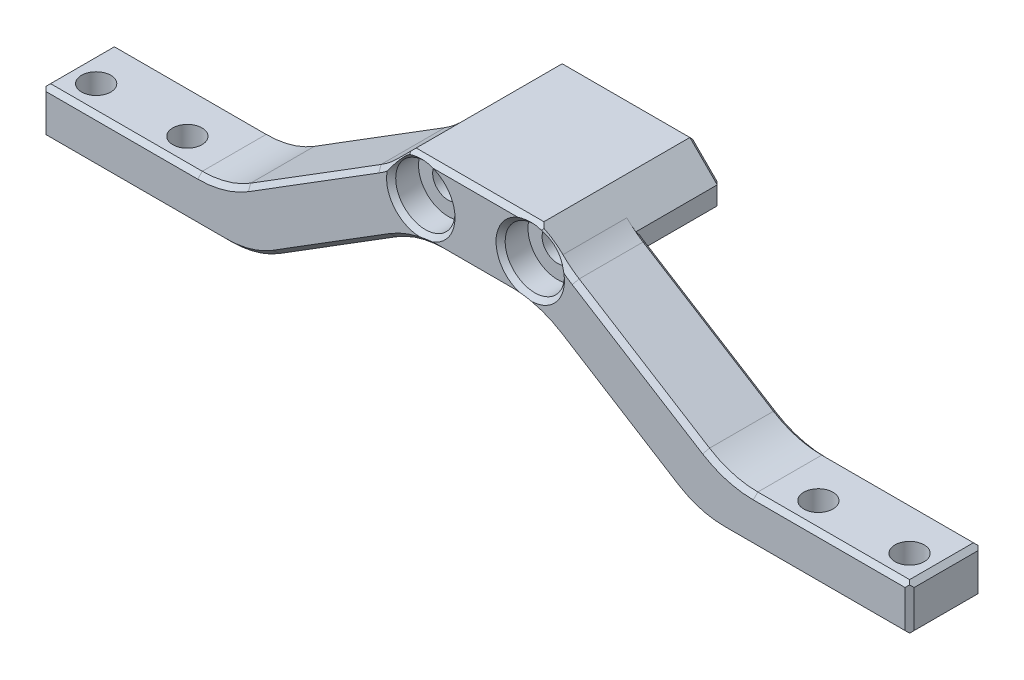
SolidWorks part; units mm, degrees
material "5052-H38"
ref_plane "Front" through (0, 0, 0) normal (0, 0, 1) x (1, 0, 0)
ref_plane "Top" through (0, 0, 0) normal (0, 1, 0) x (1, 0, 0)
ref_plane "Right" through (0, 0, 0) normal (1, 0, 0) x (0, 0, -1)
sketch "ｽｹｯﾁ2" plane through (0, 0, 0) normal (0, 0, 1) x (1, 0, 0)
  line L4 (87.5, 41.7504) -> (73.5, 41.7504)
  line L5 (70.5, 38.7504) -> (70.5, 36.7504)
  line L6 (73.5, 33.7504) -> (87.5, 33.7504)
  line L7 (90.5, 36.7504) -> (90.5, 38.7504)
  line L8 (87.5, 41.7504) -> (73.5, 41.7504)
  line L9 (70.5, 38.7504) -> (70.5, 36.7504)
  line L10 (73.5, 33.7504) -> (87.5, 33.7504)
  line L11 (90.5, 36.7504) -> (90.5, 38.7504)
  line L16 (70.5, 38.7504) -> (73.5, 41.7504)
  line L17 (70.5, 36.7504) -> (73.5, 33.7504)
  line L18 (87.5, 33.7504) -> (90.5, 36.7504)
  line L19 (90.5, 38.7504) -> (87.5, 41.7504)
  arc A4 (90.5, 38.7504) -> (87.5, 41.7504) centre (87.5, 38.7504) ccw
  arc A5 (73.5, 41.7504) -> (70.5, 38.7504) centre (73.5, 38.7504) ccw
  arc A6 (70.5, 36.7504) -> (73.5, 33.7504) centre (73.5, 36.7504) ccw
  arc A7 (87.5, 33.7504) -> (90.5, 36.7504) centre (87.5, 36.7504) ccw
  arc A8 (90.5, 38.7504) -> (87.5, 41.7504) centre (87.5, 38.7504) ccw construction
  arc A9 (73.5, 41.7504) -> (70.5, 38.7504) centre (73.5, 38.7504) ccw construction
  arc A10 (70.5, 36.7504) -> (73.5, 33.7504) centre (73.5, 36.7504) ccw construction
  arc A11 (87.5, 33.7504) -> (90.5, 36.7504) centre (87.5, 36.7504) ccw construction
  dimension "D1" = 0
extrude "ﾎﾞｽ - 押し出し1" add sketch "ｽｹｯﾁ2" along normal blind 17
sketch "ｽｹｯﾁ5" plane through (0, 0, 17) normal (0, 0, 1) x (1, 0, 0)
  line L0 (74.5, 37.7504) -> (54.5, 25.2705) construction
  line L1 (56.0882, 22.7254) -> (76.0882, 35.2052)
  line L2 (56.0882, 22.7254) -> (52.9118, 27.8157) construction
  line L3 (76.0882, 35.2052) -> (72.9118, 40.2955)
  line L4 (52.9118, 27.8157) -> (72.9118, 40.2955)
  line L5 (56.0882, 22.7254) -> (72.9118, 40.2955) construction
  line L6 (76.0882, 35.2052) -> (52.9118, 27.8157) construction
  line L7 (80.5, 41.7504) -> (80.5, 33.7004) construction
  line L8 (87.5, 41.7504) -> (73.5, 41.7504) construction
  line L9 (84.9118, 35.2052) -> (108.0882, 27.8157) construction
  line L10 (104.9118, 22.7254) -> (88.0882, 40.2955) construction
  line L11 (86.5, 37.7504) -> (106.5, 25.2705) construction
  line L12 (108.0882, 27.8157) -> (88.0882, 40.2955)
  line L13 (84.9118, 35.2052) -> (88.0882, 40.2955)
  line L14 (104.9118, 22.7254) -> (108.0882, 27.8157) construction
  line L15 (104.9118, 22.7254) -> (84.9118, 35.2052)
  line L16 (35.2152, 22.7254) -> (119.9925, 22.7254) construction
  line L17 (52.9118, 27.8157) -> (32.9118, 27.8157)
  line L18 (32.9118, 27.8157) -> (32.9118, 22.7254)
  line L19 (32.9118, 22.7254) -> (56.0882, 22.7254)
  line L20 (128.0882, 22.7254) -> (104.9118, 22.7254)
  line L21 (128.0882, 27.8157) -> (128.0882, 22.7254)
  line L22 (108.0882, 27.8157) -> (128.0882, 27.8157)
  line L23 (73.5, 33.7504) -> (87.5, 33.7504) construction
  arc A0 (105.9294, 18.5905) -> (55.0706, 18.5905) centre (80.5, 0.0004) ccw construction
  arc A1 (105.9294, 18.5905) -> (55.0706, 18.5905) centre (80.5, 0.0004) ccw construction
  point P4 (64.5, 31.5104)
  point P22 (96.5, 31.5104)
  point P25 (80.5, 37.7254)
  dimension "D1" = 20
  dimension "D2" = 20
  dimension "D3" = 6
  dimension "D4" = 15
  dimension "D5" = 6
  dimension "D6" = 4
extrude "ﾎﾞｽ - 押し出し3" add sketch "ｽｹｯﾁ5" against normal blind 8
sketch "ｽｹｯﾁ7" plane through (0, 0, 17) normal (0, 0, 1) x (1, 0, 0)
  line L0 (87.5, 41.7504) -> (73.5, 41.7504) construction
  line L1 (80.5, 41.7504) -> (80.5, 33.7504) construction
  line L2 (73.7566, 33.7504) -> (87.2434, 33.7504) construction
  circle A2 centre (74.5, 37.7504) radius 1.6
  circle A3 centre (86.5, 37.7504) radius 1.6
  dimension "D1" = 4
  dimension "D2" = 4
  dimension "D3" = 6
  dimension "D4" = 6
fillet "ﾌｨﾚｯﾄ3" radius 10 6 edges at (73.7566, 33.7504, 13) (87.2434, 33.7504, 13) (52.9118, 27.8157, 13) (56.0882, 22.7254, 13) (108.0882, 27.8157, 13) (104.9118, 22.7254, 13)
sketch "ｽｹｯﾁ13" plane through (0, 41.7504, 0) normal (0, 1, 0) x (1, 0, 0)
  line L0 (32.8181, -14) -> (128.1819, -14) construction
  line L1 (32.9118, -9) -> (32.9118, -17) construction
  line L2 (70.6068, -17) -> (55.3416, -17) construction
  line L3 (80.5, 0) -> (80.5, -17) construction
  line L4 (87.5, 0) -> (73.5, 0) construction
  circle A0 centre (35.9118, -14) radius 1.5
  circle A1 centre (125.0882, -14) radius 1.5
  circle A2 centre (45.9118, -14) radius 1.5
  circle A3 centre (115.0882, -14) radius 1.5
  dimension "D1" = 3
  dimension "D2" = 3
  dimension "D3" = 10
  dimension "D4" = 3
hole_wizard "M3 すきま穴1" positions "ｽｹｯﾁ14" profile "ｽｹｯﾁ15" hole size "M3" standard "JIS"
sketch "ｽｹｯﾁ14" plane through (0, 27.8157, 0) normal (0, 1, 0) x (1, 0, 0)
  point P0 (35.9118, -14)
  point P3 (125.0882, -14)
  point P7 (45.9118, -14)
  point P10 (115.0882, -14)
sketch "ｽｹｯﾁ15" plane through (35.9118, 27.8157, 14) normal (1, 0, 0) x (0, 0, 1)
  line L0 (0, 0) -> (0, 9.4614)
  line L1 (0, 9.4614) -> (1.6, 8.5)
  line L2 (1.6, 8.5) -> (1.6, 0)
  line L5 (1.6, 0) -> (0, 0)
  line L10 (0, 9.4614) -> (-1.6, 8.5) construction
  line L11 (0, -6.35) -> (0, 107.95) construction
  dimension "穴の直径" = 3.2
  dimension "穴の深さ" = 8.5
  dimension "ﾄﾞﾘﾙ角度" = 118
hole_wizard "M3 穴付きねじ用座ぐり穴1" positions "ｽｹｯﾁ16" profile "ｽｹｯﾁ17" counterbore size "M3" standard "JIS" end condition through all
sketch "ｽｹｯﾁ16" plane through (0, 0, 17) normal (0, 0, 1) x (1, 0, 0)
  point P0 (74.5, 37.7504)
  point P3 (86.5, 37.7504)
sketch "ｽｹｯﾁ17" plane through (74.5, 37.7504, 17) normal (1, 0, 0) x (0, -1, 0)
  line L0 (0, 0) -> (0, 17)
  line L1 (0, 17) -> (1.7, 17)
  line L3 (1.7, 17) -> (1.7, 3)
  line L4 (1.7, 3) -> (3.25, 3)
  line L5 (3.25, 3) -> (3.25, 0)
  line L7 (3.25, 0) -> (0, 0)
  line L11 (0, -6.35) -> (0, 107.95) construction
  dimension "通し穴の直径" = 3.4
  dimension "通し穴の深さ" = 17
  dimension "座ぐり穴の直径" = 6.5
  dimension "座ぐり穴の深さ" = 3
fillet "ﾌｨﾚｯﾄ4" radius 10 2 edges at (70.6068, 38.8572, 13) (90.3932, 38.8572, 13)
chamfer "面取り4" distance 0.5 angle 45 10 edges at (80.5, 41.7504, 0) (72, 40.2504, 0) (70.5, 37.7504, 0) (72, 35.2504, 0) (80.5, 33.7504, 0) (89, 35.2504, 0) (90.5, 37.7504, 0) (89, 40.2504, 0) (88.2, 37.7504, 0) (76.2, 37.7504, 0)
chamfer "面取り6" distance 0.5 angle 45 2 edges at (89.75, 37.7504, 17) (77.75, 37.7504, 17)
chamfer "面取り7" distance 0.5 angle 45 4 edges at (128.0882, 22.7254, 13) (128.0882, 27.8157, 13) (32.9118, 22.7254, 13) (32.9118, 27.8157, 13)
chamfer "面取り8" distance 0.5 angle 45 18 edges at (128.0882, 25.2705, 9) (32.9118, 25.2705, 9) (41.7298, 27.8157, 9) (70.5664, 38.9081, 9) (52.8011, 28.2022, 9) (62.4896, 33.7921, 9) (43.318, 22.7254, 9) (55.9775, 23.1119, 9) (73.8673, 33.3639, 9) (64.9224, 28.2379, 9) (119.2702, 27.8157, 9) (108.1989, 28.2022, 9) (90.4336, 38.9081, 9) (98.5104, 33.7921, 9) (117.682, 22.7254, 9) (87.1327, 33.3639, 9) (105.0225, 23.1119, 9) (96.0776, 28.2379, 9)
chamfer "面取り9" distance 0.5 angle 45 20 edges at (128.0882, 25.2705, 17) (32.9118, 25.2705, 17) (43.318, 22.7254, 17) (55.9775, 23.1119, 17) (64.9224, 28.2379, 17) (73.8673, 33.3639, 17) (80.5, 33.7504, 17) (87.1327, 33.3639, 17) (96.0776, 28.2379, 17) (117.682, 22.7254, 17) (105.0225, 23.1119, 17) (90.5913, 38.7854, 17) (119.2702, 27.8157, 17) (98.5104, 33.7921, 17) (108.1989, 28.2022, 17) (70.4087, 38.7854, 17) (62.4896, 33.7921, 17) (41.7298, 27.8157, 17) (52.8011, 28.2022, 17) (80.5, 41.7504, 17)
